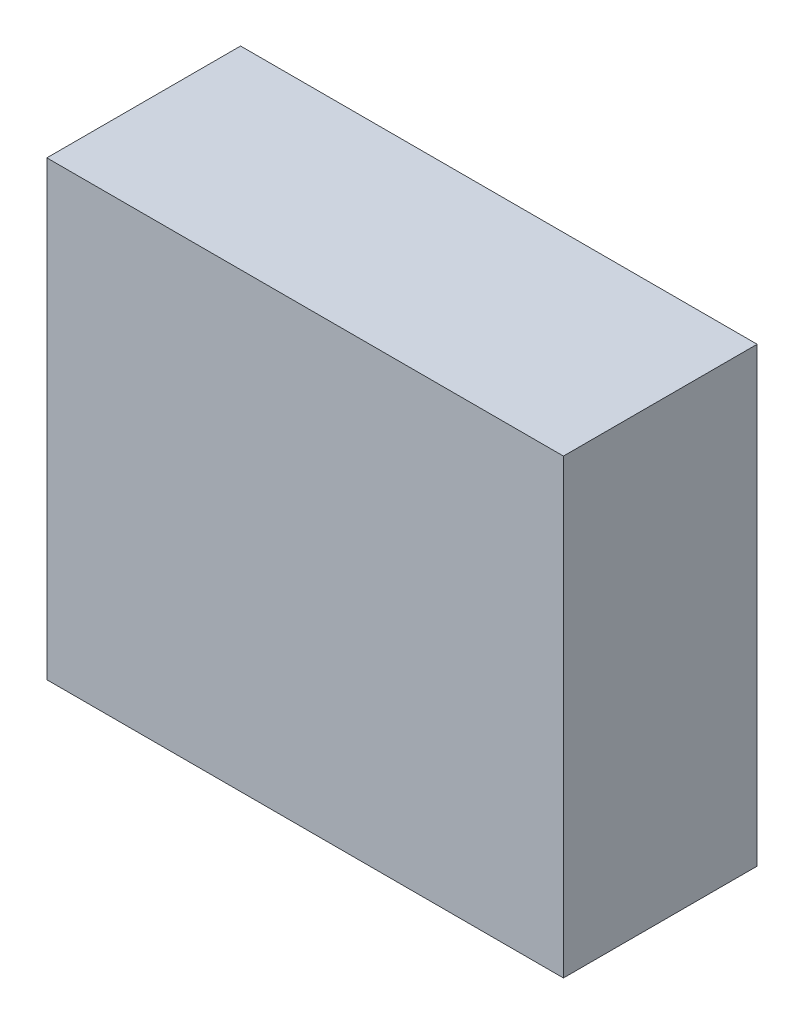
SolidWorks part; units mm, degrees
ref_plane "Front Plane" through (0, 0, 0) normal (0, 0, 1) x (1, 0, 0)
ref_plane "Top Plane" through (0, 0, 0) normal (0, 1, 0) x (1, 0, 0)
ref_plane "Right Plane" through (0, 0, 0) normal (1, 0, 0) x (0, 0, -1)
sketch "Sketch1" plane through (0, 0, 0) normal (0, 0, 1) x (1, 0, 0)
  line L1 (-50.8, 44.45) -> (50.8, 44.45)
  line L2 (-50.8, 44.45) -> (-50.8, -44.45)
  line L3 (-50.8, -44.45) -> (50.8, -44.45)
  line L4 (50.8, 44.45) -> (50.8, -44.45)
  line L5 (-50.8, 44.45) -> (50.8, -44.45) construction
  line L6 (-50.8, -44.45) -> (50.8, 44.45) construction
  point P0 (0, 0)
  dimension "D1" = 101.6
  dimension "D2" = 88.9
extrude "Boss-Extrude1" add sketch "Sketch1" along normal blind 19.05 and the other way blind 19.05
